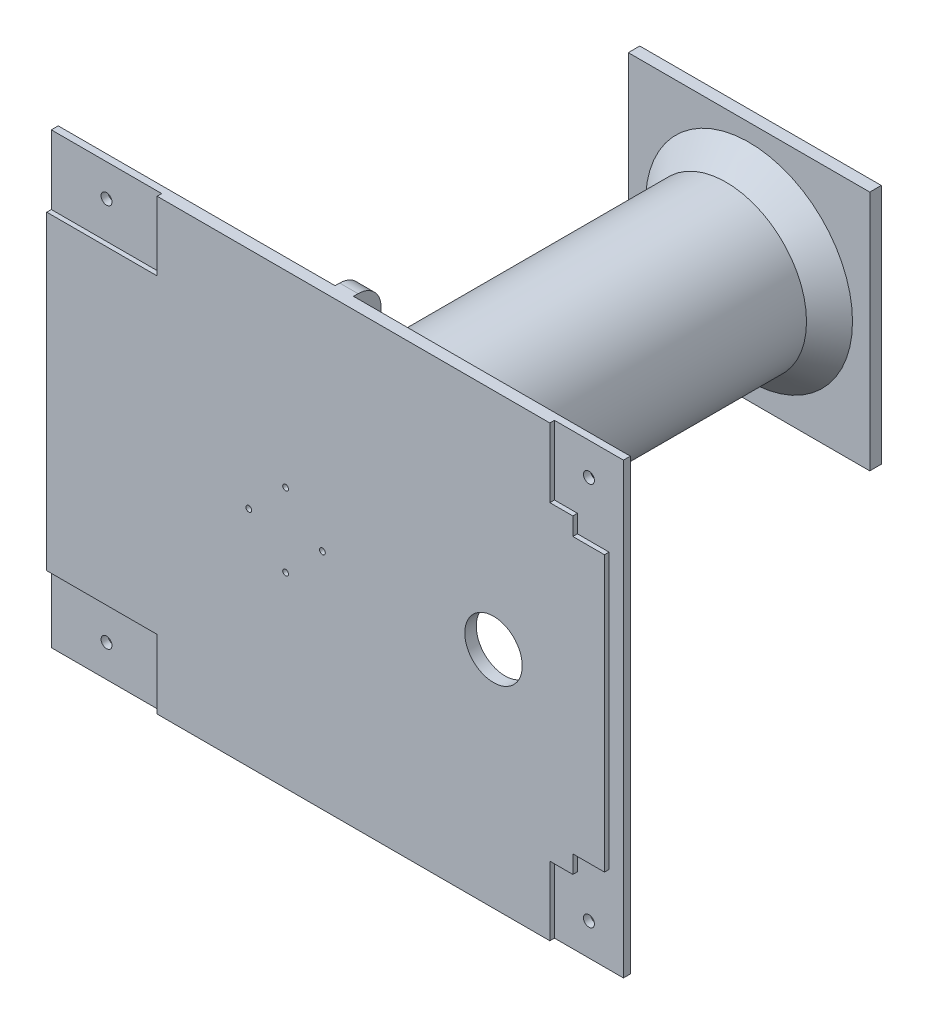
SolidWorks part; units mm, degrees
ref_plane "Alzado" through (0, 0, 0) normal (0, 0, 1) x (1, 0, 0)
ref_plane "Planta" through (0, 0, 0) normal (0, 1, 0) x (1, 0, 0)
ref_plane "Vista lateral" through (0, 0, 0) normal (1, 0, 0) x (0, 0, -1)
sketch "Croquis1" plane through (0, 0, 0) normal (0, 0, 1) x (1, 0, 0)
  line L1 (-117.2917, 97.7627) -> (131.4683, 97.7627)
  line L2 (-117.2917, 97.7627) -> (-117.2917, -97.2373)
  line L3 (-117.2917, -97.2373) -> (131.4683, -97.2373)
  line L4 (131.4683, 97.7627) -> (131.4683, -97.2373)
  dimension "D1" = 248.76
  dimension "D2" = 195
extrude "Saliente-Extruir1" add sketch "Croquis1" along normal blind 5
sketch "Croquis2" plane through (0, 0, 5) normal (0, 0, 1) x (1, 0, 0)
  line L0 (-117.2917, 0.2627) -> (131.4683, 0.2627) construction
  line L1 (-117.2917, 97.7627) -> (-117.2917, -97.2373) construction
  line L2 (131.4683, -97.2373) -> (131.4683, 97.7627) construction
  line L3 (-117.2917, -97.2373) -> (-69.2917, -97.2373)
  line L4 (-117.2917, -97.2373) -> (131.4683, -97.2373) construction
  line L5 (-69.2917, -97.2373) -> (-69.2917, -67.2373)
  line L6 (-69.2917, -67.2373) -> (-117.2917, -67.2373)
  line L7 (-117.2917, -67.2373) -> (-117.2917, -97.2373)
  line L8 (131.4683, 67.7627) -> (101.4683, 67.7627)
  line L9 (131.4683, -97.2373) -> (101.4683, -97.2373)
  line L10 (131.4683, -97.2373) -> (131.4683, -67.2373)
  line L11 (131.4683, -67.2373) -> (101.4683, -67.2373)
  line L12 (101.4683, -97.2373) -> (101.4683, -67.2373)
  line L13 (101.4683, 97.7627) -> (101.4683, 67.7627)
  line L14 (131.4683, 97.7627) -> (101.4683, 97.7627)
  line L15 (131.4683, 97.7627) -> (131.4683, 67.7627)
  line L16 (-69.2917, 67.7627) -> (-117.2917, 67.7627)
  line L17 (-69.2917, 97.7627) -> (-69.2917, 67.7627)
  line L18 (-117.2917, 97.7627) -> (-69.2917, 97.7627)
  line L19 (-117.2917, 67.7627) -> (-117.2917, 97.7627)
  dimension "D1" = 48
  dimension "D2" = 30
  dimension "D3" = 30
  dimension "D4" = 30
extrude "Cortar-Extruir1" cut sketch "Croquis2" against normal blind 2
sketch "Croquis3" plane through (0, 0, 5) normal (0, 0, 1) x (1, 0, 0)
  line L0 (-69.2917, 97.7627) -> (-117.2917, 97.7627) construction
  line L1 (116.4683, 83.7627) -> (116.4683, 67.7627) construction
  line L3 (116.4683, -83.2373) -> (116.4683, -67.2373) construction
  line L5 (131.4683, -67.2373) -> (101.4683, -67.2373) construction
  line L6 (101.4683, 67.7627) -> (131.4683, 67.7627) construction
  line L7 (-93.2917, 83.7627) -> (-93.2917, 67.7627) construction
  line L8 (-117.2917, 67.7627) -> (-69.2917, 67.7627) construction
  line L9 (-93.2917, -83.2373) -> (-93.2917, -67.2373) construction
  line L10 (-69.2917, -67.2373) -> (-117.2917, -67.2373) construction
  circle A0 centre (-93.2917, 83.7627) radius 2.375
  circle A1 centre (-93.2917, -83.2373) radius 2.375
  circle A2 centre (116.4683, 83.7627) radius 2.375
  circle A3 centre (116.4683, -83.2373) radius 2.375
  dimension "D2" = 4.75
  dimension "D3" = 4.75
  dimension "D5" = 4.75
  dimension "D6" = 4.75
  dimension "D1" = 14
  dimension "D4" = 14
  dimension "D7" = 209.76
  dimension "D8" = 16
  dimension "D9" = 16
extrude "Cortar-Extruir2" cut sketch "Croquis3" against normal blind 10
sketch "Croquis4" plane through (0, 0, 0) normal (0, 0, -1) x (-1, 0, 0)
  line L7 (-131.4683, 97.7627) -> (117.2917, 97.7627) construction
  line L9 (117.2917, 97.7627) -> (117.2917, -97.2373) construction
  circle A0 centre (13.4317, 0.2627) radius 35
  dimension "D3" = 70
  dimension "D1" = 103.86
  dimension "D2" = 97.5
extrude "Saliente-Extruir2" add sketch "Croquis4" along normal blind 196.5 contours A0
sketch "Croquis5" plane through (0, 0, 0) normal (0, 0, -1) x (-1, 0, 0)
  line L0 (-131.4683, 0.2627) -> (117.2917, 0.2627) construction
  line L1 (-131.4683, -97.2373) -> (-131.4683, 97.7627) construction
  line L2 (117.2917, 97.7627) -> (117.2917, -97.2373) construction
  circle A0 centre (-76.9683, 0.2627) radius 12.5
  dimension "D1" = 25
  dimension "D2" = 54.5
extrude "Cortar-Extruir3" cut sketch "Croquis5" against normal blind 10
sketch "Croquis6" plane through (0, 0, 0) normal (0, 0, -1) x (-1, 0, 0)
  line L0 (-131.4683, 97.7627) -> (117.2917, 97.7627) construction
  line L1 (-7.0883, 97.7627) -> (-7.0883, -97.2373)
  line L2 (117.2917, -97.2373) -> (-131.4683, -97.2373) construction
  line L3 (-7.0883, 97.7627) -> (117.2917, 97.7627)
  line L4 (117.2917, 97.7627) -> (117.2917, -97.2373)
  line L5 (117.2917, -97.2373) -> (-7.0883, -97.2373)
  line L6 (-131.4683, 0.2627) -> (56.0317, 0.2627)
  line L7 (-131.4683, -97.2373) -> (-131.4683, 97.7627) construction
  circle A1 centre (56.0317, 0.2627) radius 100
  dimension "D1" = 200
  dimension "D2" = 187.5
sketch "Croquis9" plane through (0, 97.7627, 0) normal (0, 1, 0) x (1, 0, 0)
  line L0 (7.0883, 0) -> (7.0883, -5)
  line L1 (131.4683, 0) -> (-117.2917, 0) construction
  line L2 (101.4683, -5) -> (-69.2917, -5) construction
ref_plane "Plano3" through (7.0883, 0, 0) normal (1, 0, 0) x (0, 0, -1)
sketch "Croquis12" plane through (7.0883, 0, 0) normal (1, 0, 0) x (0, 0, -1)
  line L0 (0, 97.7627) -> (0, 67.7627)
  line L1 (0, 67.7627) -> (12, 67.7627)
  line L2 (12, 67.7627) -> (12, 97.7627)
  line L3 (12, 97.7627) -> (0, 97.7627)
  line L4 (0, -97.2373) -> (12, -97.2373)
  line L5 (12, -97.2373) -> (12, -67.2373)
  line L6 (12, -67.2373) -> (0, -67.2373)
  line L7 (0, -67.2373) -> (0, -97.2373)
  dimension "D1" = 30
  dimension "D2" = 12
  dimension "D3" = 30
  dimension "D4" = 12
extrude "Saliente-Extruir3" add sketch "Croquis12" along normal mid plane 8
fillet "Redondeo1" radius 10 2 edges at (7.0883, -67.2373, 0) (7.0883, 67.7627, 0)
fillet "Redondeo2" radius 10 2 edges at (7.0883, 67.7627, -12) (7.0883, -67.2373, -12)
fillet "Redondeo3" radius 10 2 edges at (7.0883, -97.2373, -12) (7.0883, 97.7627, -12)
sketch "Croquis13" plane through (11.0883, 0, 0) normal (1, 0, 0) x (0, 0, -1)
  line L0 (-5, 0.2627) -> (196.5, 0.2627) construction
  line L1 (-5, -67.2373) -> (-5, 67.7627) construction
  line L2 (196.5, -34.7373) -> (196.5, 35.2627) construction
  line L3 (6, 87.7627) -> (12, 87.7627) construction
  line L4 (6, 87.7627) -> (6, 77.7627) construction
  circle A0 centre (6, 87.7627) radius 1.625
  circle A1 centre (6, 77.7627) radius 1.625
  circle A2 centre (6, -77.2373) radius 1.625
  circle A3 centre (6, -87.2373) radius 1.625
  dimension "D3" = 3.25
  dimension "D4" = 3.25
  dimension "D1" = 6
extrude "Cortar-Extruir5" cut sketch "Croquis13" against normal through all both and the other way through all
sketch "Croquis14" plane through (0, 0, 0) normal (0, 0, -1) x (-1, 0, 0)
  line L0 (-7.0883, 97.7627) -> (-7.0883, -97.2373)
  line L1 (-7.0883, 97.7627) -> (117.2917, 97.7627)
  line L2 (117.2917, 97.7627) -> (117.2917, -97.2373)
  line L3 (117.2917, -97.2373) -> (-7.0883, -97.2373)
sketch "Croquis15" plane through (0, 0, 5) normal (0, 0, 1) x (1, 0, 0)
  line L0 (111.4683, 67.7627) -> (131.4683, 67.7627)
  line L1 (111.4683, 67.7627) -> (111.4683, 60.0127)
  line L2 (131.4683, -67.2373) -> (101.4683, -67.2373) construction
  line L3 (111.4683, -67.2373) -> (111.4683, -59.4873)
  line L4 (111.4683, -59.4873) -> (125.2183, -59.4873)
  line L5 (125.2183, -59.4873) -> (125.2183, 60.0127)
  line L6 (111.4683, 60.0127) -> (125.2183, 60.0127)
  line L7 (111.4683, -67.2373) -> (131.4683, -67.2373)
  line L10 (131.4683, -67.2373) -> (131.4683, 67.7627)
  dimension "D1" = 119.5
  dimension "D2" = 7.75
  dimension "D3" = 13.75
extrude "Cortar-Extruir7" cut sketch "Croquis15" against normal blind 2
sketch "Croquis16" plane through (0, 0, -196.5) normal (0, 0, -1) x (-1, 0, 0)
  line L1 (-39.0683, -52.2373) -> (65.9317, -52.2373)
  line L2 (-39.0683, -52.2373) -> (-39.0683, 52.7627)
  line L3 (-39.0683, 52.7627) -> (65.9317, 52.7627)
  line L4 (65.9317, -52.2373) -> (65.9317, 52.7627)
  line L5 (-39.0683, -52.2373) -> (65.9317, 52.7627) construction
  line L6 (-39.0683, 52.7627) -> (65.9317, -52.2373) construction
  point P0 (13.4317, 0.2627)
  dimension "D1" = 105
  dimension "D2" = 105
extrude "Saliente-Extruir4" add sketch "Croquis16" along normal blind 5
fillet "Chaflán1" radius 10 1 edges at (-48.4317, 0.2627, -196.5) type face fillet profile chamfer first side face at (-48.4317, 0.2627, -196.5) second side face at (-48.4317, 0.2627, -196.5)
sketch "Croquis17" plane through (0, 0, 5) normal (0, 0, 1) x (1, 0, 0)
  circle A0 centre (-13.4317, 0) radius 35
  dimension "D2" = 70
sketch "Croquis18" plane through (0, 0, 5) normal (0, 0, 1) x (1, 0, 0)
  line L0 (-13.4317, 0) -> (-13.4317, 16) construction
  circle A0 centre (-13.4317, 16) radius 1.25
  circle A1 centre (2.5683, 0) radius 1.25
  circle A2 centre (-13.4317, -16) radius 1.25
  circle A3 centre (-29.4317, 0) radius 1.25
  dimension "D2" = 2.5
  dimension "D1" = 16
  dimension "D3" = 4
extrude "Cortar-Extruir8" cut sketch "Croquis18" against normal blind 5
